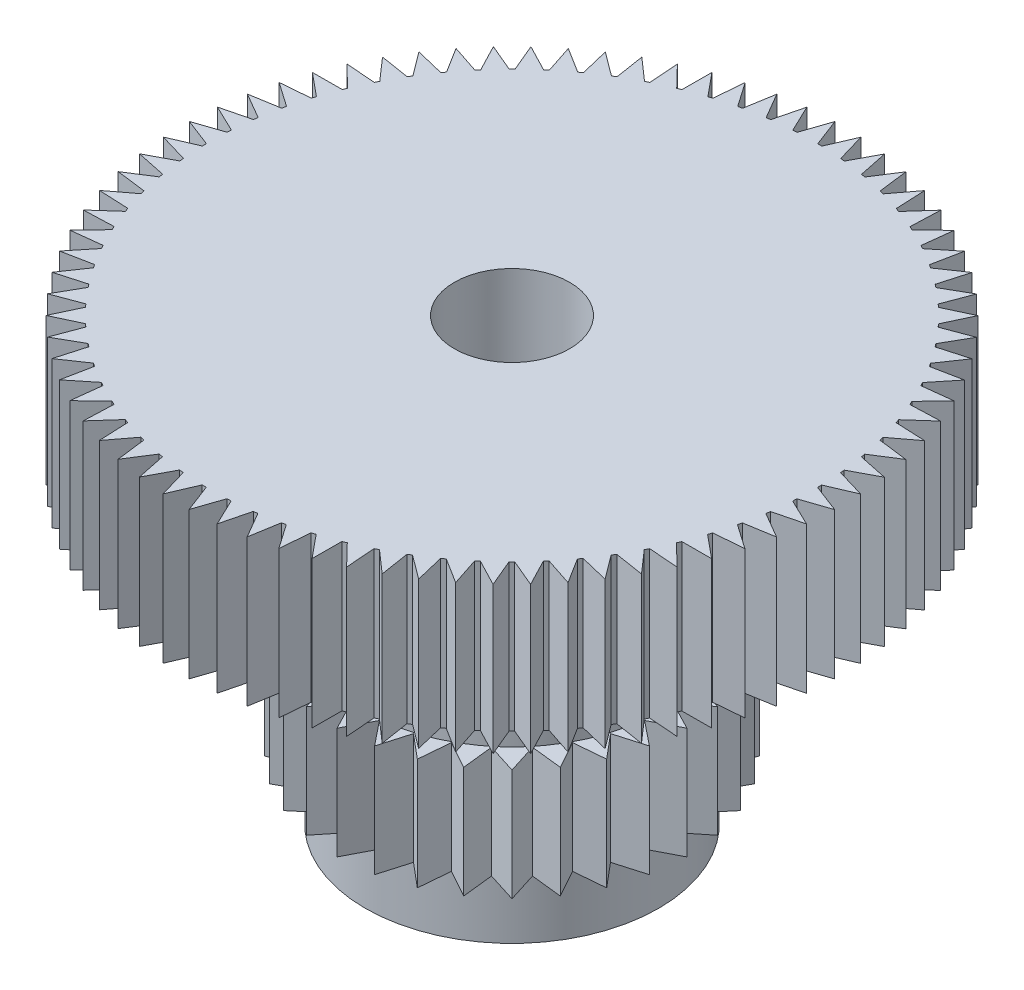
SolidWorks part; units mm, degrees
ref_plane "Front Plane" through (0, 0, 0) normal (0, 0, 1) x (1, 0, 0)
ref_plane "Top Plane" through (0, 0, 0) normal (0, 1, 0) x (1, 0, 0)
ref_plane "Right Plane" through (0, 0, 0) normal (1, 0, 0) x (0, 0, -1)
sketch "Sketch1" plane through (0, 0, 0) normal (0, 1, 0) x (1, 0, 0)
  circle A0 centre (0, 0) radius 6.35
  dimension "D1" = 12.7
extrude "Boss-Extrude1" add sketch "Sketch1" along normal blind 12.7 contours A0
sketch "Sketch2" plane through (0, 12.7, 0) normal (0, 1, 0) x (1, 0, 0)
  circle A0 centre (0, 0) radius 14.2875
  dimension "D1" = 28.575
extrude "Boss-Extrude2" add sketch "Sketch2" along normal blind 6.35
sketch "Sketch3" plane through (0, 0, 0) normal (0, -1, 0) x (1, 0, 0)
  circle A0 centre (0, 0) radius 2.4943
extrude "Cut-Extrude1" cut sketch "Sketch3" against normal blind 27.432
sketch "Sketch4" plane through (0, 19.05, 0) normal (0, 1, 0) x (1, 0, 0)
  line L2 (-10.4804, 9.675) -> (-9.2933, 9.1746)
  line L3 (-10.4804, 9.675) -> (-9.8869, 8.5316)
  line L4 (-9.6679, 10.487) -> (-8.5249, 9.8927)
  line L5 (-9.6679, 10.487) -> (-9.1683, 9.2995)
  line L6 (-8.7927, 11.2309) -> (-7.7012, 10.5466)
  line L7 (-8.7927, 11.2309) -> (-8.3903, 10.0071)
  line L8 (-7.8605, 11.902) -> (-6.8276, 11.1321)
  line L9 (-7.8605, 11.902) -> (-7.5578, 10.6498)
  line L10 (-6.8773, 12.4959) -> (-5.9097, 11.6454)
  line L11 (-6.8773, 12.4959) -> (-6.6764, 11.2234)
  line L12 (-5.8495, 13.0088) -> (-4.9535, 12.0831)
  line L13 (-5.8495, 13.0088) -> (-5.7516, 11.7242)
  line L14 (-4.7837, 13.4373) -> (-3.9651, 12.4425)
  line L15 (-4.7837, 13.4373) -> (-4.7896, 12.149)
  line L16 (-3.687, 13.7787) -> (-2.9511, 12.7213)
  line L17 (-3.687, 13.7787) -> (-3.7964, 12.495)
  line L18 (-2.5663, 14.0307) -> (-1.9178, 12.9175)
  line L19 (-2.5663, 14.0307) -> (-2.7787, 12.76)
  line L20 (-1.429, 14.1917) -> (-0.8722, 13.0299)
  line L21 (-1.429, 14.1917) -> (-1.7429, 12.9422)
  line L22 (-0.2824, 14.2606) -> (0.1791, 13.0578)
  line L23 (-0.2824, 14.2606) -> (-0.6959, 13.0405)
  line L24 (0.866, 14.2371) -> (1.2292, 13.0011)
  line L25 (0.866, 14.2371) -> (0.3557, 13.0542)
  line L26 (2.0088, 14.1212) -> (2.2714, 12.86)
  line L27 (2.0088, 14.1212) -> (1.405, 12.9833)
  line L28 (3.1386, 13.9138) -> (3.2988, 12.6355)
  line L29 (3.1386, 13.9138) -> (2.4451, 12.8281)
  line L30 (4.248, 13.6161) -> (4.3049, 12.3291)
  line L31 (4.248, 13.6161) -> (3.4695, 12.5898)
  line L32 (5.3299, 13.2302) -> (5.283, 11.9427)
  line L33 (5.3299, 13.2302) -> (4.4713, 12.2698)
  line L34 (6.3772, 12.7584) -> (6.2269, 11.4789)
  line L35 (6.3772, 12.7584) -> (5.4441, 11.8702)
  line L36 (7.3832, 12.2039) -> (7.1303, 10.9406)
  line L37 (7.3832, 12.2039) -> (6.3816, 11.3936)
  line L38 (8.3412, 11.5702) -> (7.9876, 10.3314)
  line L39 (8.3412, 11.5702) -> (7.2777, 10.8432)
  line L40 (9.2452, 10.8615) -> (8.793, 9.6552)
  line L41 (9.2452, 10.8615) -> (8.1266, 10.2224)
  line L42 (10.0892, 10.0823) -> (9.5414, 8.9163)
  line L43 (10.0892, 10.0823) -> (8.9228, 9.5353)
  line L44 (10.8678, 9.2378) -> (10.2279, 8.1196)
  line L45 (10.8678, 9.2378) -> (9.6611, 8.7864)
  line L46 (11.5759, 8.3333) -> (10.8481, 7.2703)
  line L47 (11.5759, 8.3333) -> (10.3368, 7.9805)
  line L48 (12.2089, 7.3749) -> (11.398, 6.3738)
  line L49 (12.2089, 7.3749) -> (10.9455, 7.1229)
  line L50 (12.7627, 6.3685) -> (11.8739, 5.436)
  line L51 (12.7627, 6.3685) -> (11.4831, 6.219)
  line L52 (13.2338, 5.3209) -> (12.2728, 4.4629)
  line L53 (13.2338, 5.3209) -> (11.9463, 5.2749)
  line L54 (13.619, 4.2388) -> (12.5921, 3.4609)
  line L55 (13.619, 4.2388) -> (12.332, 4.2965)
  line L56 (13.9159, 3.1292) -> (12.8298, 2.4364)
  line L57 (13.9159, 3.1292) -> (12.6378, 3.2902)
  line L58 (14.1226, 1.9992) -> (12.9842, 1.3962)
  line L59 (14.1226, 1.9992) -> (12.8615, 2.2627)
  line L60 (14.2377, 0.8564) -> (13.0544, 0.3468)
  line L61 (14.2377, 0.8564) -> (13.0019, 1.2204)
  line L62 (14.2604, -0.2921) -> (13.04, -0.7047)
  line L63 (14.2604, -0.2921) -> (13.0579, 0.1702)
  line L64 (14.1907, -1.4386) -> (12.941, -1.7517)
  line L65 (14.1907, -1.4386) -> (13.0293, -0.8811)
  line L66 (14.0289, -2.5758) -> (12.7581, -2.7874)
  line L67 (14.0289, -2.5758) -> (12.9162, -1.9266)
  line L68 (13.7761, -3.6963) -> (12.4925, -3.8049)
  line L69 (13.7761, -3.6963) -> (12.7192, -2.9597)
  line L70 (13.434, -4.7929) -> (12.1458, -4.7978)
  line L71 (13.434, -4.7929) -> (12.4398, -3.9736)
  line L72 (13.0048, -5.8583) -> (11.7203, -5.7596)
  line L73 (13.0048, -5.8583) -> (12.0798, -4.9617)
  line L74 (12.4912, -6.8858) -> (11.2189, -6.684)
  line L75 (12.4912, -6.8858) -> (11.6413, -5.9176)
  line L76 (11.8967, -7.8686) -> (10.6446, -7.5651)
  line L77 (11.8967, -7.8686) -> (11.1274, -6.8352)
  line L78 (11.2249, -8.8003) -> (10.0014, -8.3971)
  line L79 (11.2249, -8.8003) -> (10.5413, -7.7084)
  line L80 (10.4804, -9.675) -> (9.2933, -9.1746)
  line L81 (10.4804, -9.675) -> (9.8869, -8.5316)
  line L82 (9.6679, -10.487) -> (8.5249, -9.8927)
  line L83 (9.6679, -10.487) -> (9.1683, -9.2995)
  line L84 (8.7927, -11.2309) -> (7.7012, -10.5466)
  line L85 (8.7927, -11.2309) -> (8.3903, -10.0071)
  line L86 (7.8605, -11.902) -> (6.8276, -11.1321)
  line L87 (7.8605, -11.902) -> (7.5578, -10.6498)
  line L88 (6.8773, -12.4959) -> (5.9097, -11.6454)
  line L89 (6.8773, -12.4959) -> (6.6764, -11.2234)
  line L90 (5.8495, -13.0088) -> (4.9535, -12.0831)
  line L91 (5.8495, -13.0088) -> (5.7516, -11.7242)
  line L92 (4.7837, -13.4373) -> (3.9651, -12.4425)
  line L93 (4.7837, -13.4373) -> (4.7896, -12.149)
  line L94 (3.687, -13.7787) -> (2.9511, -12.7213)
  line L95 (3.687, -13.7787) -> (3.7964, -12.495)
  line L96 (2.5663, -14.0307) -> (1.9178, -12.9175)
  line L97 (2.5663, -14.0307) -> (2.7787, -12.76)
  line L98 (1.429, -14.1917) -> (0.8722, -13.0299)
  line L99 (1.429, -14.1917) -> (1.7429, -12.9422)
  line L100 (0.2824, -14.2606) -> (-0.1791, -13.0578)
  line L101 (0.2824, -14.2606) -> (0.6959, -13.0405)
  line L102 (-0.866, -14.2371) -> (-1.2292, -13.0011)
  line L103 (-0.866, -14.2371) -> (-0.3557, -13.0542)
  line L104 (-2.0088, -14.1212) -> (-2.2714, -12.86)
  line L105 (-2.0088, -14.1212) -> (-1.405, -12.9833)
  line L106 (-3.1386, -13.9138) -> (-3.2988, -12.6355)
  line L107 (-3.1386, -13.9138) -> (-2.4451, -12.8281)
  line L108 (-4.248, -13.6161) -> (-4.3049, -12.3291)
  line L109 (-4.248, -13.6161) -> (-3.4695, -12.5898)
  line L110 (-5.3299, -13.2302) -> (-5.283, -11.9427)
  line L111 (-5.3299, -13.2302) -> (-4.4713, -12.2698)
  line L112 (-6.3772, -12.7584) -> (-6.2269, -11.4789)
  line L113 (-6.3772, -12.7584) -> (-5.4441, -11.8702)
  line L114 (-7.3832, -12.2039) -> (-7.1303, -10.9406)
  line L115 (-7.3832, -12.2039) -> (-6.3816, -11.3936)
  line L116 (-8.3412, -11.5702) -> (-7.9876, -10.3314)
  line L117 (-8.3412, -11.5702) -> (-7.2777, -10.8432)
  line L118 (-9.2452, -10.8615) -> (-8.793, -9.6552)
  line L119 (-9.2452, -10.8615) -> (-8.1266, -10.2224)
  line L120 (-10.0892, -10.0823) -> (-9.5414, -8.9163)
  line L121 (-10.0892, -10.0823) -> (-8.9228, -9.5353)
  line L122 (-10.8678, -9.2378) -> (-10.2279, -8.1196)
  line L123 (-10.8678, -9.2378) -> (-9.6611, -8.7864)
  line L124 (-11.5759, -8.3333) -> (-10.8481, -7.2703)
  line L125 (-11.5759, -8.3333) -> (-10.3368, -7.9805)
  line L126 (-12.2089, -7.3749) -> (-11.398, -6.3738)
  line L127 (-12.2089, -7.3749) -> (-10.9455, -7.1229)
  line L128 (-12.7627, -6.3685) -> (-11.8739, -5.436)
  line L129 (-12.7627, -6.3685) -> (-11.4831, -6.219)
  line L130 (-13.2338, -5.3209) -> (-12.2728, -4.4629)
  line L131 (-13.2338, -5.3209) -> (-11.9463, -5.2749)
  line L132 (-13.619, -4.2388) -> (-12.5921, -3.4609)
  line L133 (-13.619, -4.2388) -> (-12.332, -4.2965)
  line L134 (-13.9159, -3.1292) -> (-12.8298, -2.4364)
  line L135 (-13.9159, -3.1292) -> (-12.6378, -3.2902)
  line L136 (-14.1226, -1.9992) -> (-12.9842, -1.3962)
  line L137 (-14.1226, -1.9992) -> (-12.8615, -2.2627)
  line L138 (-14.2377, -0.8564) -> (-13.0544, -0.3468)
  line L139 (-14.2377, -0.8564) -> (-13.0019, -1.2204)
  line L140 (-14.2604, 0.2921) -> (-13.04, 0.7047)
  line L141 (-14.2604, 0.2921) -> (-13.0579, -0.1702)
  line L142 (-14.1907, 1.4386) -> (-12.941, 1.7517)
  line L143 (-14.1907, 1.4386) -> (-13.0293, 0.8811)
  line L144 (-14.0289, 2.5758) -> (-12.7581, 2.7874)
  line L145 (-14.0289, 2.5758) -> (-12.9162, 1.9266)
  line L146 (-13.7761, 3.6963) -> (-12.4925, 3.8049)
  line L147 (-13.7761, 3.6963) -> (-12.7192, 2.9597)
  line L148 (-13.434, 4.7929) -> (-12.1458, 4.7978)
  line L149 (-13.434, 4.7929) -> (-12.4398, 3.9736)
  line L150 (-13.0048, 5.8583) -> (-11.7203, 5.7596)
  line L151 (-13.0048, 5.8583) -> (-12.0798, 4.9617)
  line L152 (-12.4912, 6.8858) -> (-11.2189, 6.684)
  line L153 (-12.4912, 6.8858) -> (-11.6413, 5.9176)
  line L154 (-11.8967, 7.8686) -> (-10.6446, 7.5651)
  line L155 (-11.8967, 7.8686) -> (-11.1274, 6.8352)
  line L156 (-11.2249, 8.8003) -> (-10.0014, 8.3971)
  line L157 (-11.2249, 8.8003) -> (-10.5413, 7.7084)
  arc A0 (-7.5578, 10.6498) -> (-7.7012, 10.5466) centre (0, 0) ccw
  arc A1 (-1.7429, 12.9422) -> (-1.9178, 12.9175) centre (0, 0) ccw
  arc A2 (-0.2824, 14.2606) -> (-1.429, 14.1917) centre (0, 0) ccw
  arc A3 (-8.3903, 10.0071) -> (-8.5249, 9.8927) centre (0, 0) ccw
  arc A4 (-9.1683, 9.2995) -> (-9.2933, 9.1746) centre (0, 0) ccw
  arc A5 (-9.8869, 8.5316) -> (-10.0014, 8.3971) centre (0, 0) ccw
  arc A6 (-10.5413, 7.7084) -> (-10.6446, 7.5651) centre (0, 0) ccw
  arc A7 (-11.1274, 6.8352) -> (-11.2189, 6.684) centre (0, 0) ccw
  arc A8 (-11.6413, 5.9176) -> (-11.7203, 5.7596) centre (0, 0) ccw
  arc A9 (-12.0798, 4.9617) -> (-12.1458, 4.7978) centre (0, 0) ccw
  arc A10 (-12.4398, 3.9736) -> (-12.4925, 3.8049) centre (0, 0) ccw
  arc A11 (-12.7192, 2.9597) -> (-12.7581, 2.7874) centre (0, 0) ccw
  arc A12 (-12.9162, 1.9266) -> (-12.941, 1.7517) centre (0, 0) ccw
  arc A13 (-13.0293, 0.8811) -> (-13.04, 0.7047) centre (0, 0) ccw
  arc A14 (-13.0579, -0.1702) -> (-13.0544, -0.3468) centre (0, 0) ccw
  arc A15 (-13.0019, -1.2204) -> (-12.9842, -1.3962) centre (0, 0) ccw
  arc A16 (-12.8615, -2.2627) -> (-12.8298, -2.4364) centre (0, 0) ccw
  arc A17 (-12.332, -4.2965) -> (-12.2728, -4.4629) centre (0, 0) ccw
  arc A18 (-11.9463, -5.2749) -> (-11.8739, -5.436) centre (0, 0) ccw
  arc A19 (-12.6378, -3.2902) -> (-12.5921, -3.4609) centre (0, 0) ccw
  arc A20 (-11.4831, -6.219) -> (-11.398, -6.3738) centre (0, 0) ccw
  arc A21 (-10.9455, -7.1229) -> (-10.8481, -7.2703) centre (0, 0) ccw
  arc A22 (-10.3368, -7.9805) -> (-10.2279, -8.1196) centre (0, 0) ccw
  arc A23 (-9.6611, -8.7864) -> (-9.5414, -8.9163) centre (0, 0) ccw
  arc A24 (-8.9228, -9.5353) -> (-8.793, -9.6552) centre (0, 0) ccw
  arc A25 (-8.1266, -10.2224) -> (-7.9876, -10.3314) centre (0, 0) ccw
  arc A26 (-7.2777, -10.8432) -> (-7.1303, -10.9406) centre (0, 0) ccw
  arc A27 (-6.3816, -11.3936) -> (-6.2269, -11.4789) centre (0, 0) ccw
  arc A28 (-5.4441, -11.8702) -> (-5.283, -11.9427) centre (0, 0) ccw
  arc A29 (-4.4713, -12.2698) -> (-4.3049, -12.3291) centre (0, 0) ccw
  arc A30 (-3.4695, -12.5898) -> (-3.2988, -12.6355) centre (0, 0) ccw
  arc A31 (-2.4451, -12.8281) -> (-2.2714, -12.86) centre (0, 0) ccw
  arc A32 (-1.405, -12.9833) -> (-1.2292, -13.0011) centre (0, 0) ccw
  arc A33 (-0.3557, -13.0542) -> (-0.1791, -13.0578) centre (0, 0) ccw
  arc A34 (0.6959, -13.0405) -> (0.8722, -13.0299) centre (0, 0) ccw
  arc A35 (1.7429, -12.9422) -> (1.9178, -12.9175) centre (0, 0) ccw
  arc A36 (2.7787, -12.76) -> (2.9511, -12.7213) centre (0, 0) ccw
  arc A37 (3.7964, -12.495) -> (3.9651, -12.4425) centre (0, 0) ccw
  arc A38 (4.7896, -12.149) -> (4.9535, -12.0831) centre (0, 0) ccw
  arc A39 (5.7516, -11.7242) -> (5.9097, -11.6454) centre (0, 0) ccw
  arc A40 (6.6764, -11.2234) -> (6.8276, -11.1321) centre (0, 0) ccw
  arc A41 (7.5578, -10.6498) -> (7.7012, -10.5466) centre (0, 0) ccw
  arc A42 (8.3903, -10.0071) -> (8.5249, -9.8927) centre (0, 0) ccw
  arc A43 (9.1683, -9.2995) -> (9.2933, -9.1746) centre (0, 0) ccw
  arc A44 (9.8869, -8.5316) -> (10.0014, -8.3971) centre (0, 0) ccw
  arc A45 (10.5413, -7.7084) -> (10.6446, -7.5651) centre (0, 0) ccw
  arc A46 (-6.6764, 11.2234) -> (-6.8276, 11.1321) centre (0, 0) ccw
  arc A47 (-5.7516, 11.7242) -> (-5.9097, 11.6454) centre (0, 0) ccw
  arc A48 (-4.7896, 12.149) -> (-4.9535, 12.0831) centre (0, 0) ccw
  arc A49 (-3.7964, 12.495) -> (-3.9651, 12.4425) centre (0, 0) ccw
  arc A50 (-2.7787, 12.76) -> (-2.9511, 12.7213) centre (0, 0) ccw
  arc A51 (-0.6959, 13.0405) -> (-0.8722, 13.0299) centre (0, 0) ccw
  arc A52 (0.3557, 13.0542) -> (0.1791, 13.0578) centre (0, 0) ccw
  arc A53 (1.405, 12.9833) -> (1.2292, 13.0011) centre (0, 0) ccw
  arc A54 (2.4451, 12.8281) -> (2.2714, 12.86) centre (0, 0) ccw
  arc A55 (3.4695, 12.5898) -> (3.2988, 12.6355) centre (0, 0) ccw
  arc A56 (4.4713, 12.2698) -> (4.3049, 12.3291) centre (0, 0) ccw
  arc A57 (5.4441, 11.8702) -> (5.283, 11.9427) centre (0, 0) ccw
  arc A58 (6.3816, 11.3936) -> (6.2269, 11.4789) centre (0, 0) ccw
  arc A59 (7.2777, 10.8432) -> (7.1303, 10.9406) centre (0, 0) ccw
  arc A60 (8.1266, 10.2224) -> (7.9876, 10.3314) centre (0, 0) ccw
  arc A61 (8.9228, 9.5353) -> (8.793, 9.6552) centre (0, 0) ccw
  arc A62 (9.6611, 8.7864) -> (9.5414, 8.9163) centre (0, 0) ccw
  arc A63 (10.3368, 7.9805) -> (10.2279, 8.1196) centre (0, 0) ccw
  arc A64 (10.9455, 7.1229) -> (10.8481, 7.2703) centre (0, 0) ccw
  arc A65 (11.4831, 6.219) -> (11.398, 6.3738) centre (0, 0) ccw
  arc A66 (11.9463, 5.2749) -> (11.8739, 5.436) centre (0, 0) ccw
  arc A67 (12.332, 4.2965) -> (12.2728, 4.4629) centre (0, 0) ccw
  arc A68 (12.6378, 3.2902) -> (12.5921, 3.4609) centre (0, 0) ccw
  arc A69 (12.8615, 2.2627) -> (12.8298, 2.4364) centre (0, 0) ccw
  arc A70 (13.0019, 1.2204) -> (12.9842, 1.3962) centre (0, 0) ccw
  arc A71 (13.0579, 0.1702) -> (13.0544, 0.3468) centre (0, 0) ccw
  arc A72 (13.0293, -0.8811) -> (13.04, -0.7047) centre (0, 0) ccw
  arc A73 (12.9162, -1.9266) -> (12.941, -1.7517) centre (0, 0) ccw
  arc A74 (12.0798, -4.9617) -> (12.1458, -4.7978) centre (0, 0) ccw
  arc A75 (12.4398, -3.9736) -> (12.4925, -3.8049) centre (0, 0) ccw
  arc A76 (12.7192, -2.9597) -> (12.7581, -2.7874) centre (0, 0) ccw
  arc A77 (11.6413, -5.9176) -> (11.7203, -5.7596) centre (0, 0) ccw
  arc A78 (11.1274, -6.8352) -> (11.2189, -6.684) centre (0, 0) ccw
  circle A79 centre (0, 0) radius 16.3548
  arc A80 (6.3772, 12.7584) -> (0.866, 14.2371) centre (0, 0) ccw
  arc A82 (-4.248, -13.6161) -> (-3.1386, -13.9138) centre (0, 0) ccw
  circle M2 centre (0, 0) radius 14.2875
  dimension "D1" = 78
extrude "Cut-Extrude5" cut sketch "Sketch4" against normal blind 7.366 contours A82 L108 A29 L111 L110 A28 L113 L112 A27 L115 L114 A26 L117 L116 A25 L119 L118 A24 L121 L120 A23 L123 L122 A22 L125 L124 A21 L127 L126 A20 L129 L128 A18 L131 L130 A17 L133 L132 A19 L135 L134 A16 L137 L136 A15 L139 L138 A14 L141 M2 | A79 M2 | L109 A82 L106 A30 | A51 L23 A2 L20 | L27 A80 L24 A53 | L29 A80 L26 A54 | L31 A80 L28 A55 | L33 A80 L30 A56 | L35 A80 L32 A57
sketch "Sketch5" plane through (0, 0, 0) normal (0, -1, 0) x (1, 0, 0)
  line L0 (-1.477, -7.4256) -> (-1.8567, -6.1209)
  line L2 (0.6269, -6.3655) -> (0, -7.571)
  line L3 (0, -7.571) -> (-0.6269, -6.3655)
  line L4 (-0.6269, -6.3655) -> (-1.477, -7.4256)
  line L5 (-2.8973, -6.9947) -> (-3.0152, -5.641)
  line L6 (-1.8567, -6.1209) -> (-2.8973, -6.9947)
  line L7 (-4.2062, -6.2951) -> (-4.0578, -4.9444)
  line L8 (-3.0152, -5.641) -> (-4.2062, -6.2951)
  line L9 (-5.3535, -5.3535) -> (-4.9444, -4.0578)
  line L10 (-4.0578, -4.9444) -> (-5.3535, -5.3535)
  line L11 (-6.2951, -4.2062) -> (-5.641, -3.0152)
  line L12 (-4.9444, -4.0578) -> (-6.2951, -4.2062)
  line L13 (-6.9947, -2.8973) -> (-6.1209, -1.8567)
  line L14 (-5.641, -3.0152) -> (-6.9947, -2.8973)
  line L15 (-7.4256, -1.477) -> (-6.3655, -0.6269)
  line L16 (-6.1209, -1.8567) -> (-7.4256, -1.477)
  line L17 (-7.571, 0) -> (-6.3655, 0.6269)
  line L18 (-6.3655, -0.6269) -> (-7.571, 0)
  line L19 (-7.4256, 1.477) -> (-6.1041, 1.8616)
  line L20 (-6.3655, 0.6269) -> (-7.4256, 1.477)
  line L21 (-6.9947, 2.8973) -> (-5.641, 3.0152)
  line L22 (-6.1096, 1.8434) -> (-6.9947, 2.8973)
  line L23 (-6.2951, 4.2062) -> (-4.9444, 4.0578)
  line L24 (-5.641, 3.0152) -> (-6.2951, 4.2062)
  line L25 (-5.3535, 5.3535) -> (-4.0578, 4.9444)
  line L26 (-4.9444, 4.0578) -> (-5.3535, 5.3535)
  line L27 (-4.2062, 6.2951) -> (-3.0152, 5.641)
  line L28 (-4.0578, 4.9444) -> (-4.2062, 6.2951)
  line L29 (-2.8973, 6.9947) -> (-1.8567, 6.1209)
  line L30 (-3.0152, 5.641) -> (-2.8973, 6.9947)
  line L31 (-1.477, 7.4256) -> (-0.6269, 6.3655)
  line L32 (-1.8567, 6.1209) -> (-1.477, 7.4256)
  line L33 (0, 7.571) -> (0.6269, 6.3655)
  line L34 (-0.6269, 6.3655) -> (0, 7.571)
  line L35 (1.477, 7.4256) -> (1.8567, 6.1209)
  line L36 (0.6269, 6.3655) -> (1.477, 7.4256)
  line L37 (2.8973, 6.9947) -> (3.0152, 5.641)
  line L38 (1.8567, 6.1209) -> (2.8973, 6.9947)
  line L39 (4.2062, 6.2951) -> (4.0578, 4.9444)
  line L40 (3.0152, 5.641) -> (4.2062, 6.2951)
  line L41 (5.3535, 5.3535) -> (4.9444, 4.0578)
  line L42 (4.0578, 4.9444) -> (5.3535, 5.3535)
  line L43 (6.2951, 4.2062) -> (5.641, 3.0152)
  line L44 (4.9444, 4.0578) -> (6.2951, 4.2062)
  line L45 (6.9947, 2.8973) -> (6.1209, 1.8567)
  line L46 (5.641, 3.0152) -> (6.9947, 2.8973)
  line L47 (7.4256, 1.477) -> (6.3655, 0.6269)
  line L48 (6.1209, 1.8567) -> (7.4256, 1.477)
  line L49 (7.571, 0) -> (6.3655, -0.6269)
  line L50 (6.3655, 0.6269) -> (7.571, 0)
  line L51 (7.4256, -1.477) -> (6.1209, -1.8567)
  line L52 (6.3655, -0.6269) -> (7.4256, -1.477)
  line L53 (6.9947, -2.8973) -> (5.641, -3.0152)
  line L54 (6.1209, -1.8567) -> (6.9947, -2.8973)
  line L55 (6.2951, -4.2062) -> (4.9444, -4.0578)
  line L56 (5.641, -3.0152) -> (6.2951, -4.2062)
  line L57 (5.3535, -5.3535) -> (4.0578, -4.9444)
  line L58 (4.9444, -4.0578) -> (5.3535, -5.3535)
  line L59 (4.2062, -6.2951) -> (3.0152, -5.641)
  line L60 (4.0578, -4.9444) -> (4.2062, -6.2951)
  line L61 (2.8973, -6.9947) -> (1.8567, -6.1209)
  line L62 (3.0152, -5.641) -> (2.8973, -6.9947)
  line L63 (1.477, -7.4256) -> (0.6269, -6.3655)
  line L64 (1.8567, -6.1209) -> (1.477, -7.4256)
  point P9 (0, -6.35)
  dimension "D2" = 32
extrude "Boss-Extrude3" add sketch "Sketch5" against normal blind 4.826 from offset 2.54
